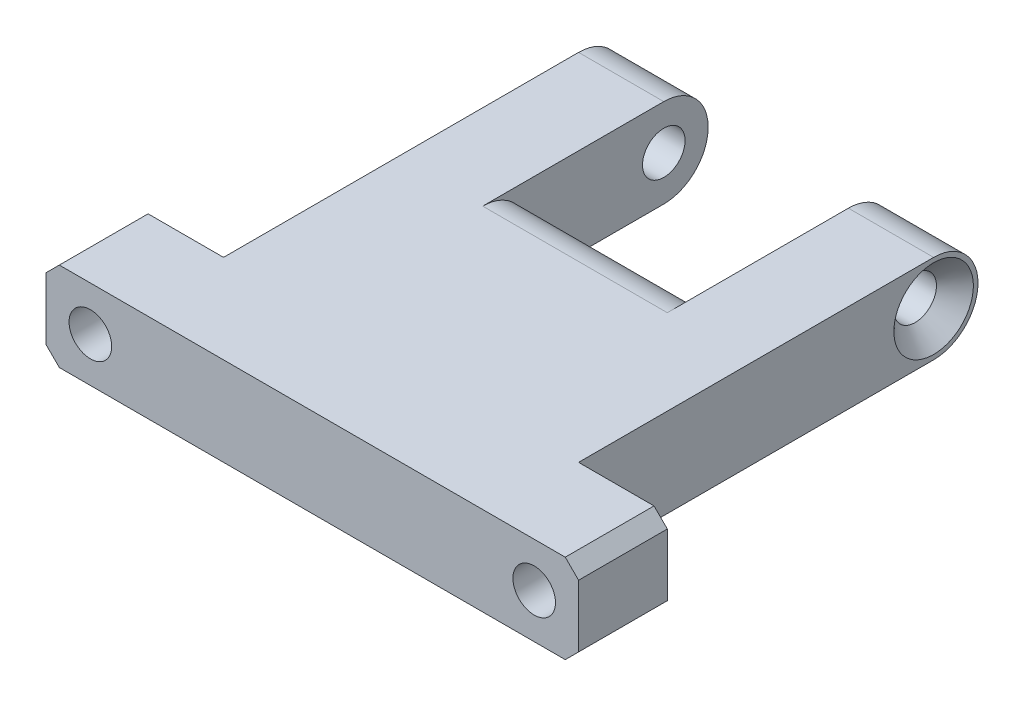
SolidWorks part; units mm, degrees
ref_plane "Front Plane" through (0, 0, 0) normal (0, 0, 1) x (1, 0, 0)
ref_plane "Top Plane" through (0, 0, 0) normal (0, 1, 0) x (1, 0, 0)
ref_plane "Right Plane" through (0, 0, 0) normal (1, 0, 0) x (0, 0, -1)
sketch "Sketch1" plane through (0, 0, 0) normal (0, 1, 0) x (1, 0, 0)
  line L1 (-30, -27.5) -> (30, -27.5)
  line L2 (-30, -27.5) -> (-30, 27.5)
  line L3 (-30, 27.5) -> (30, 27.5)
  line L4 (30, -27.5) -> (30, 27.5)
  line L5 (-30, -27.5) -> (30, 27.5) construction
  line L6 (-30, 27.5) -> (30, -27.5) construction
  line L7 (-10.4, 7.1) -> (10.4, 7.1)
  line L8 (-10.4, 7.1) -> (-10.4, 27.5)
  line L9 (-10.4, 27.5) -> (10.4, 27.5)
  line L10 (10.4, 7.1) -> (10.4, 27.5)
  line L11 (-10.4, 7.1) -> (10.4, 27.5) construction
  line L12 (-10.4, 27.5) -> (10.4, 7.1) construction
  line L13 (30, 27.5) -> (20, 27.5)
  line L14 (30, 27.5) -> (30, -17.5)
  line L15 (30, -17.5) -> (20, -17.5)
  line L16 (20, 27.5) -> (20, -17.5)
  line L17 (-30, 27.5) -> (-20, 27.5)
  line L18 (-30, 27.5) -> (-30, -17.5)
  line L19 (-30, -17.5) -> (-20, -17.5)
  line L20 (-20, 27.5) -> (-20, -17.5)
  point P0 (0, 0)
  point P6 (0, 17.3)
  point P11 (0, 27.5)
  point P12 (0, 27.5)
  dimension "D1" = 55
  dimension "D2" = 60
  dimension "D3" = 20.8
  dimension "D4" = 20.4
  dimension "D5" = 10
  dimension "D6" = 10
extrude "Boss-Extrude1" add sketch "Sketch1" along normal blind 10 contours L3 L20 L19 L2 L1 L4 L15 L16 L10 L7 L8 region at (0, 0, 5.9932)
fillet "Fillet1" radius 5 6 edges at (-15.2, 0, -27.5) (15.2, 0, -27.5) (-15.2, 10, -27.5) (15.2, 10, -27.5) (0, 10, -7.1) (0, 0, -7.1)
chamfer "Chamfer1" distance 1.5 angle 45 4 edges at (-30, 10, 22.5) (-30, 0, 22.5) (30, 10, 22.5) (30, 0, 22.5)
hole_wizard "CSK for M4 SFHCS1" positions "Sketch2" profile "Sketch3" countersink size "M4" standard "ANSI Metric" end condition through all
sketch "Sketch2" plane through (0, 0, 17.5) normal (0, 0, -1) x (-1, 0, 0)
  line L1 (-28.5, 10) -> (-20, 10) construction
  point P0 (-25, 5)
  point P2 (25, 5)
  dimension "D1" = 5
  dimension "D2" = 5
  dimension "D3" = 5
sketch "Sketch3" plane through (25, 5, 17.5) normal (1, 0, 0) x (0, 1, 0)
  line L0 (0, 0) -> (0, 10)
  line L1 (0, 10) -> (2.4, 10)
  line L2 (2.4, 10) -> (2.4, 2.08)
  line L3 (2.4, 2.08) -> (4.48, 0)
  line L5 (4.48, 0) -> (0, 0)
  line L6 (-2.4, 2.08) -> (-4.48, 0) construction
  line L11 (0, -6.35) -> (0, 107.95) construction
  dimension "Thru Hole Dia." = 4.8
  dimension "Thru Hole Depth" = 10
  dimension "Near C'Sink Dia." = 8.96
  dimension "Near C'Sink Angle" = 90
hole_wizard "CSK for M4 SFHCS2" positions "Sketch4" profile "Sketch5" countersink size "M4" standard "ANSI Metric" end condition up to next
sketch "Sketch4" plane through (-20, 0, 0) normal (-1, 0, 0) x (0, 0, 1)
  line L0 (-22.5, 0) -> (-22.5, 10)
  point P7 (-22.5, 5)
sketch "Sketch5" plane through (-20, 5, -22.5) normal (0, 1, 0) x (0, 0, 1)
  line L0 (0, 0) -> (0, 9.6)
  line L1 (0, 9.6) -> (2.4, 9.6)
  line L2 (2.4, 9.6) -> (2.4, 2.08)
  line L3 (2.4, 2.08) -> (4.48, 0)
  line L5 (4.48, 0) -> (0, 0)
  line L6 (-2.4, 2.08) -> (-4.48, 0) construction
  line L11 (0, -6.35) -> (0, 107.95) construction
  dimension "Thru Hole Dia." = 4.8
  dimension "Thru Hole Depth" = 9.6
  dimension "Near C'Sink Dia." = 8.96
  dimension "Near C'Sink Angle" = 90
mirror "Mirror1" about plane through (0, 0, 0) normal (1, 0, 0) of "CSK for M4 SFHCS2"
